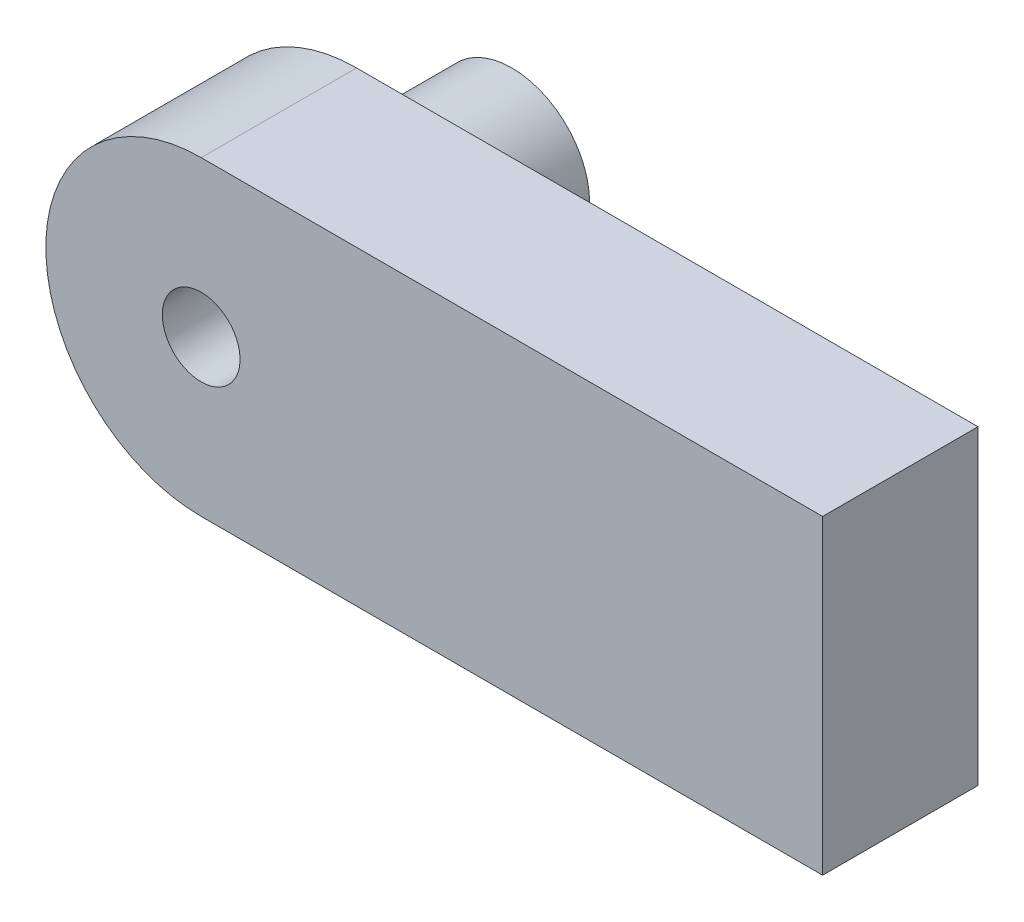
SolidWorks part; units mm, degrees
ref_plane "Piano frontale" through (0, 0, 0) normal (0, 0, 1) x (1, 0, 0)
ref_plane "Piano superiore" through (0, 0, 0) normal (0, 1, 0) x (1, 0, 0)
ref_plane "Piano destro" through (0, 0, 0) normal (1, 0, 0) x (0, 0, -1)
sketch "Schizzo1" plane through (0, 0, 0) normal (0, 0, 1) x (1, 0, 0)
  line L0 (0, 4.5035) -> (-20, 4.5035)
  line L2 (-20, -5.4965) -> (0, -5.4965)
  line L12 (0, 4.5035) -> (0, -5.4965)
  arc A0 (-20, 4.5035) -> (-20, -5.4965) centre (-20, -0.4965) ccw
  dimension "D1" = 10
  dimension "D9" = 20
extrude "Estrusione-Estrusione1" add sketch "Schizzo1" along normal blind 5
sketch "Schizzo2" plane through (0, 0, 0) normal (0, 0, -1) x (-1, 0, 0)
  arc A0 (20, -5.4965) -> (20, 4.5035) centre (20, -0.4965) ccw construction
  arc A1 (20, -5.4965) -> (20, 4.5035) centre (20, -0.4965) ccw construction
  circle A2 centre (20, -0.4965) radius 2.5
extrude "Estrusione-Estrusione2" add sketch "Schizzo2" along normal blind 5 contours A2
sketch "Schizzo3" plane through (0, 0, -5) normal (0, 0, -1) x (-1, 0, 0)
  circle A0 centre (20, -0.4965) radius 1.25
  dimension "D1" = 2.5
extrude "Taglio-Estrusione1" cut sketch "Schizzo3" against normal through all
